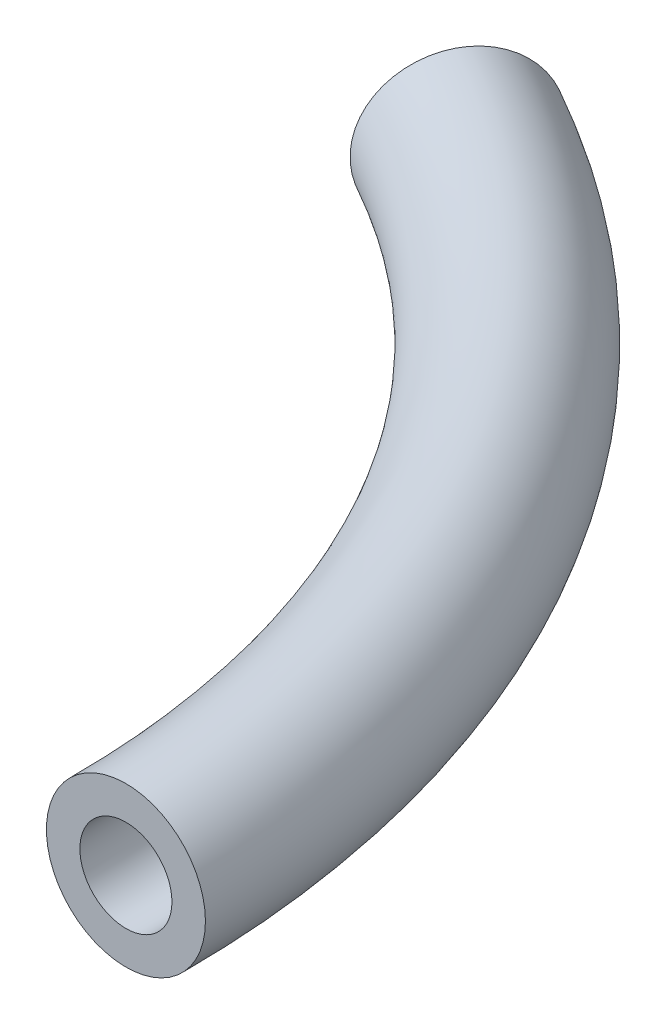
SolidWorks part; units mm, degrees
note: '?' marks a value the reader was unsure of.
ref_plane "Vorne" through (0, 0, 0) normal (0, 0, 1) x (1, 0, 0)
ref_plane "Oben" through (0, 0, 0) normal (0, 1, 0) x (1, 0, 0)
ref_plane "Rechts" through (0, 0, 0) normal (1, 0, 0) x (0, 0, -1)
sketch "Skizze1" plane through (0, 0, 0) normal (0, 1, 0) x (1, 0, 0)
  line L0 (33, 0) -> (0, 0) construction
  arc A0 (16.1153, 28.7975) -> (33, 0) centre (0, 0) cw
  dimension "D1" = 33
  dimension "D2" = 35
sketch "Skizze2" plane through (0, 0, 0) normal (0, 0, 1) x (1, 0, 0)
  circle A0 centre (33, 0) radius 2.25
  dimension "D1" = 4.5
sweep "Austragung-Dünn1" add profiles "Skizze2" path "Skizze1" parameters "D1"=1.2
ref_axis "Achse1" through (0, 3.135, 0) along (0, -1, 0)?
